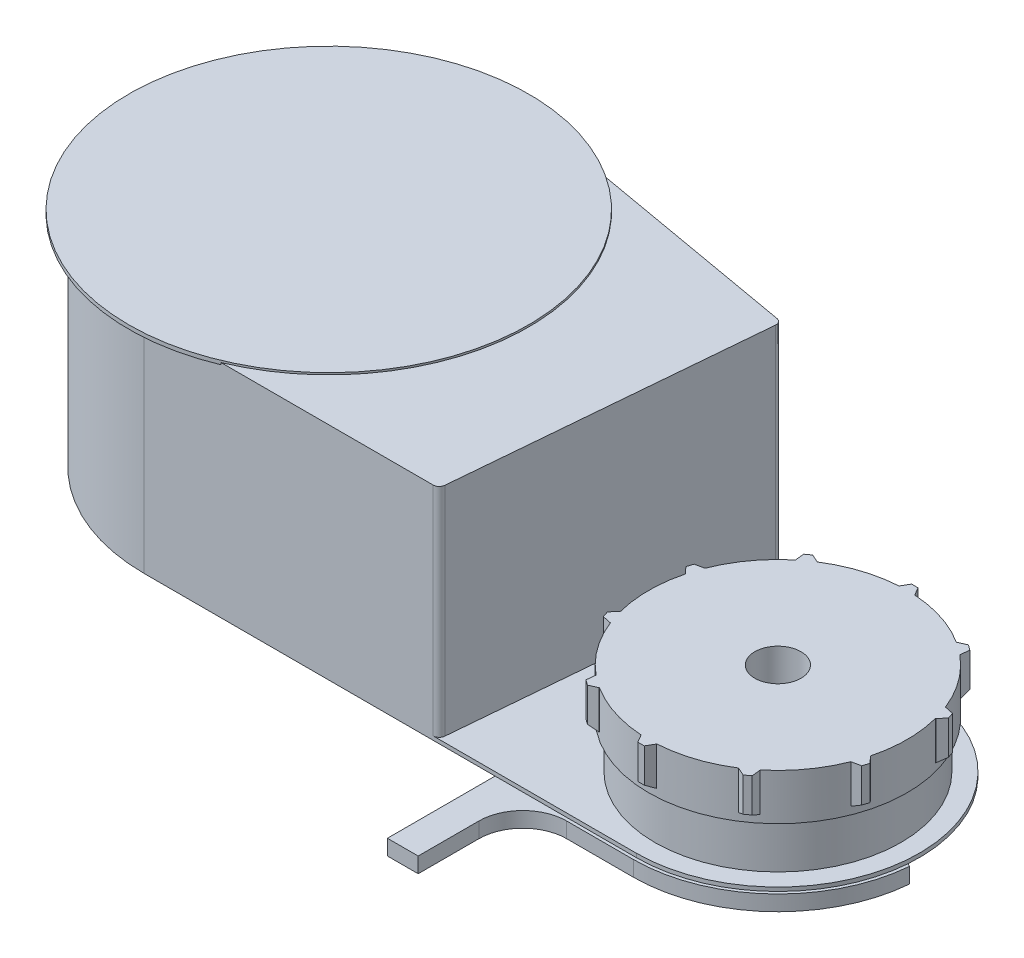
SolidWorks part; units mm, degrees
ref_plane "Front Plane" through (0, 0, 0) normal (0, 0, 1) x (1, 0, 0)
ref_plane "Top Plane" through (0, 0, 0) normal (0, 1, 0) x (1, 0, 0)
ref_plane "Right Plane" through (0, 0, 0) normal (1, 0, 0) x (0, 0, -1)
sketch "Sketch1" plane through (0, 0, 0) normal (0, 1, 0) x (1, 0, 0)
  line L0 (-203.2, -58.4223) -> (0, -58.4223)
  line L1 (-189.968, 92.82) -> (10.1449, 57.5347)
  arc A0 (-203.2, -58.4223) -> (-189.968, 92.82) centre (-203.2, 17.7777) cw
  circle A2 centre (0, 0) radius 9.525
  arc A8 (0, -58.4223) -> (10.1449, 57.5347) centre (0, 0) ccw
  point P2 (0, 0)
  point P7 (0, 0)
  dimension "D2" = 19.05
  dimension "D9" = 76.2
  dimension "D3" = 10
  dimension "D1" = 203.2
extrude "Boss-Extrude1" add sketch "Sketch1" along normal blind 1.5875
sketch "Sketch2" plane through (0, 1.5875, 0) normal (0, 1, 0) x (1, 0, 0)
  line L0 (-203.2, -58.4223) -> (0, -58.4223) construction
  line L1 (-189.968, 92.82) -> (10.1449, 57.5347) construction
  line L2 (-203.2, -58.4223) -> (-83.9298, -58.4223)
  line L3 (-189.968, 92.82) -> (-72.5098, 72.109)
  line L4 (0, 0) -> (-218.89, 19.1504) construction
  line L7 (-81.3995, -56.1037) -> (-70.4206, 69.3862)
  line L9 (-203.2, -56.8348) -> (-83.9298, -56.8348)
  line L10 (-82.981, -55.9653) -> (-72.002, 69.5246)
  line L11 (-190.2437, 91.2567) -> (-72.7855, 70.5456)
  arc A0 (-189.968, 92.82) -> (-203.2, -58.4223) centre (-203.2, 17.7777) ccw construction
  arc A1 (-189.968, 92.82) -> (-203.2, -58.4223) centre (-203.2, 17.7777) ccw
  arc A2 (-83.9298, -58.4223) -> (-81.3995, -56.1037) centre (-83.9298, -55.8823) ccw
  arc A3 (-70.4206, 69.3862) -> (-72.5098, 72.109) centre (-72.9509, 69.6076) ccw
  arc A4 (-190.2437, 91.2567) -> (-203.2, -56.8348) centre (-203.2, 17.7777) ccw
  arc A5 (-83.9298, -56.8348) -> (-82.981, -55.9653) centre (-83.9298, -55.8823) ccw
  arc A6 (-72.002, 69.5246) -> (-72.7855, 70.5456) centre (-72.9509, 69.6076) ccw
  dimension "D3" = 2.54
  dimension "D4" = 2.54
  dimension "D1" = 5
  dimension "D2" = 76.2
  dimension "D5" = 1.5875
extrude "Boss-Extrude3" add sketch "Sketch2" along normal blind 88.9
sketch "Sketch3" plane through (0, 0, 0) normal (0, -1, 0) x (1, 0, 0)
  line L0 (-58.3418, 102.8723) -> (-58.3418, -24.1083)
  line L1 (0, 0) -> (-178.2216, -15.5924) construction
  line L2 (-203.2, 58.4223) -> (0, 58.4223) construction
  line L3 (0, 0) -> (61.944, 5.4194) construction
  line L4 (-58.3418, 102.8723) -> (-45.6418, 102.8723)
  line L5 (-45.6418, 102.8723) -> (-45.6418, 77.8309)
  line L6 (0, 59.69) -> (-27.5009, 59.69)
  arc A0 (6.3428, -55.5189) -> (44.9068, -33.2559) centre (0, 0) ccw
  arc A1 (44.9068, -33.2559) -> (59.4629, 5.2023) centre (76.2, -23.1163) cw
  arc A2 (59.4629, 5.2023) -> (0, 59.69) centre (0, 0) ccw
  arc A3 (-45.6418, 77.8309) -> (-27.5009, 59.69) centre (-27.5009, 77.8309) ccw
  circle A4 centre (0, 0) radius 9.525 construction
  circle A5 centre (0, 0) radius 9.525
  spline S0 degree 3 poles (-58.3418, -24.1083) (-58.3134, -43.2841) (-57.3368, -46.3777) (-41.6621, -48.2112) (-39.6937, -54.4828) (-33.5736, -63.497) (-17.6796, -62.152) (-13.0878, -56.0963) (6.3428, -55.5189) knots 0 0 0 0 0.109377 0.144513 0.351359 0.608786 0.67365 1 1 1 1
  point P17 (0, 0)
  point P19 (0, 0)
  point P21 (-18.0951, -75.7364)
  point P23 (-35.982, -57.4236)
  point P25 (-58.3418, 58.4223)
  point P26 (-52.7333, -53.4487)
  point P28 (7.8368, -63.0146)
  point P29 (-21.0762, -77.7239)
  point P31 (-33.753, -65.2751)
  point P32 (0, 0)
  point P33 (-26.7348, -62.8639)
  point P34 (11.455, -62.4582)
  point P35 (5.7288, -63.241)
  point P36 (13.0327, -62.1482)
  point P37 (0, 0)
  dimension "D3" = 55.88
  dimension "D5" = 59.69
  dimension "D6" = 76.2
  dimension "D1" = 5
  dimension "D7" = 44.45
  dimension "D8" = 12.7
extrude "Boss-Extrude4" add sketch "Sketch3" along normal blind 6.35
sketch "Sketch4" plane through (0, 1.5875, 0) normal (0, 1, 0) x (1, 0, 0)
  circle A0 centre (0, 0) radius 50.8
  circle A1 centre (0, 0) radius 9.525 construction
  circle A2 centre (0, 0) radius 9.525
  point P11 (0, 0)
  dimension "D2" = 101.6
extrude "Boss-Extrude5" add sketch "Sketch4" along normal blind 19.05
sketch "Sketch5" plane through (0, 20.6375, 0) normal (0, 1, 0) x (1, 0, 0)
  circle A0 centre (0, 0) radius 53.34
  circle A1 centre (0, 0) radius 9.525 construction
  circle A2 centre (0, 0) radius 9.525
  dimension "D1" = 106.68
extrude "Boss-Extrude6" add sketch "Sketch5" along normal blind 19.05
ref_axis "Axis1" through (0, 53.0937, 0) along (0, -1, 0)
ref_plane "Plane1" through (0, 0, 53.34) normal (0, 0, 1) x (1, 0, 0)
sketch "Sketch6" plane through (0, 0, 53.34) normal (0, 0, 1) x (1, 0, 0)
  line L0 (53.34, 39.6875) -> (-53.34, 39.6875) construction
  line L1 (-3.175, 39.6875) -> (3.175, 39.6875)
  line L2 (-3.175, 39.6875) -> (-3.175, 23.8125)
  line L3 (-3.175, 23.8125) -> (3.175, 23.8125)
  line L4 (3.175, 39.6875) -> (3.175, 23.8125)
  line L5 (0, -0.8731) -> (0, 0.8731) construction
  dimension "D1" = 3.175
  dimension "D2" = 6.35
  dimension "D3" = 15.875
extrude "Boss-Extrude7" add sketch "Sketch6" along normal mid plane 6.35
chamfer "Chamfer3" distance 3.175 angle 30 3 edges at (3.175, 31.75, 56.515) (0, 23.8125, 56.515) (-3.175, 31.75, 56.515) first distance on face at (3.175, 31.75, 54.8802) first distance on face at (0, 23.8125, 54.9039) first distance on face at (-3.175, 31.75, 54.8802)
pattern_circular "CirPattern2" count 10 over 360 about axis through (0, 53.0937, 0) along (0, -1, 0) of "Chamfer3", "Boss-Extrude7"
sketch "Sketch8" plane through (0, 90.4875, 0) normal (0, 1, 0) x (1, 0, 0)
  line L0 (-203.2, -58.4223) -> (-83.9298, -58.4223) construction
  line L1 (-81.3995, -56.1037) -> (-70.4206, 69.3862) construction
  line L2 (-72.5098, 72.109) -> (-189.968, 92.82) construction
  line L3 (-203.2, -58.4223) -> (-83.9298, -58.4223)
  line L4 (-81.3995, -56.1037) -> (-70.4206, 69.3862)
  line L5 (-72.5098, 72.109) -> (-189.968, 92.82)
  arc A0 (-83.9298, -58.4223) -> (-81.3995, -56.1037) centre (-83.9298, -55.8823) ccw construction
  arc A1 (-70.4206, 69.3862) -> (-72.5098, 72.109) centre (-72.9509, 69.6076) ccw construction
  arc A2 (-189.968, 92.82) -> (-203.2, -58.4223) centre (-203.2, 17.7777) ccw construction
  arc A3 (-83.9298, -58.4223) -> (-81.3995, -56.1037) centre (-83.9298, -55.8823) ccw
  arc A4 (-70.4206, 69.3862) -> (-72.5098, 72.109) centre (-72.9509, 69.6076) ccw
  arc A5 (-189.968, 92.82) -> (-203.2, -58.4223) centre (-203.2, 17.7777) ccw
extrude "Boss-Extrude8" add sketch "Sketch8" along normal mid plane 1.5875
sketch "Sketch9" plane through (0, 91.2813, 0) normal (0, 1, 0) x (1, 0, 0)
  line L0 (0, 0) -> (-324.4671, 28.3872) construction
  line L1 (-53.6972, 0) -> (53.6972, 0) construction
  circle A2 centre (-203.2, 17.7777) radius 82.55
  point P5 (0, 0)
  dimension "D3" = 165.1
  dimension "D1" = 5
  dimension "D2" = 203.9762
extrude "Boss-Extrude9" add sketch "Sketch9" along normal mid plane 1.5875
